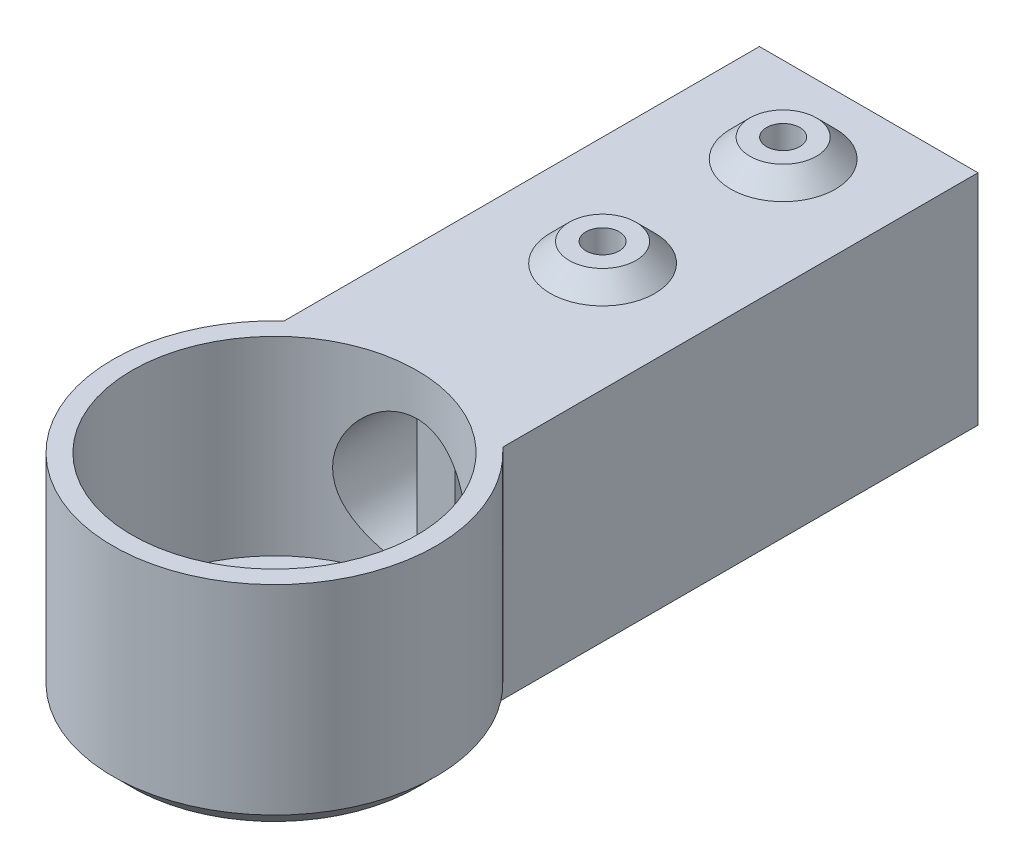
SolidWorks part; units mm, degrees
material "ABS generico"
ref_plane "Piano frontale" through (0, 0, 0) normal (0, 0, 1) x (1, 0, 0)
ref_plane "Piano superiore" through (0, 0, 0) normal (0, 1, 0) x (1, 0, 0)
ref_plane "Piano destro" through (0, 0, 0) normal (1, 0, 0) x (0, 0, -1)
sketch "Schizzo1" plane through (0, 0, 0) normal (0, 0, 1) x (1, 0, 0)
  line L4 (-7.3767, -9.877) -> (-7.3597, -9.8281)
  line L24 (7.9489, 13.813) -> (-15.0511, 13.813)
  line L25 (7.9489, 13.813) -> (7.9489, -9.187)
  line L26 (7.9489, -9.187) -> (-15.0511, -9.187)
  line L27 (-15.0511, 13.813) -> (-15.0511, -9.187)
  dimension "D1" = 23
extrude "Estrusione-Estrusione1" add sketch "Schizzo1" along normal blind 50 contours L24 L27 L26 L25 region at (-3.5511, 2.313, 0)
sketch "Schizzo3" plane through (0, 13.813, 0) normal (0, 1, 0) x (1, 0, 0)
  circle A0 centre (-3.5511, -62.52) radius 17
  dimension "D1" = 34
extrude "Taglio-Estrusione2" cut sketch "Schizzo3" against normal through all
sketch "Schizzo4" plane through (0, 13.813, 0) normal (0, 1, 0) x (1, 0, 0)
  circle A0 centre (-3.5511, -62.52) radius 17
  arc A2 (7.9489, -50) -> (-15.0511, -50) centre (-3.5511, -62.52) ccw construction
  circle A3 centre (-3.5511, -62.52) radius 15 construction
  circle A4 centre (-3.5511, -62.52) radius 15
  dimension "D1" = 34
  dimension "D2" = 30
extrude "Estrusione-Estrusione2" add sketch "Schizzo4" against normal through all contours A4 region at (-20.0702, 13.813, 62.52)
sketch "Schizzo6" plane through (0, -9.187, 0) normal (0, -1, 0) x (1, 0, 0)
  circle A0 centre (-3.5511, 62.52) radius 15
extrude "Estrusione-Estrusione3" add sketch "Schizzo6" against normal blind 2
sketch "Schizzo11" plane through (0, -7.187, 0) normal (0, 1, 0) x (1, 0, 0)
  circle A0 centre (-3.5511, -62.52) radius 15
extrude "Estrusione-Estrusione4" add sketch "Schizzo11" along normal blind 1
chamfer "Smusso2" distance 2 angle 45 1 edges at (-3.5511, -9.187, 79.52)
sketch "Schizzo12" plane through (0, -6.187, 0) normal (0, 1, 0) x (1, 0, 0)
  circle A0 centre (-3.5511, -62.52) radius 2.5
  dimension "D1" = 5
extrude "Taglio-Estrusione6" cut sketch "Schizzo12" against normal through all
sketch "Schizzo13" plane through (0, -6.187, 0) normal (0, 1, 0) x (1, 0, 0)
  circle A0 centre (-3.5511, -62.52) radius 4.75
  circle A1 centre (-3.5511, -62.52) radius 2.5 construction
  dimension "D1" = 9.5
extrude "Taglio-Estrusione7" cut sketch "Schizzo13" against normal blind 2
sketch "Schizzo14" plane through (0, -6.187, 0) normal (0, 1, 0) x (1, 0, 0)
  line L0 (-9.5708, -67.789) -> (2.4686, -57.2509) construction
  line L1 (-9.8081, -55.3716) -> (2.7059, -69.6684) construction
  circle A2 centre (-9.8081, -55.3716) radius 1.5
  circle A3 centre (2.7059, -69.6684) radius 1.5
  circle A7 centre (-9.5708, -67.789) radius 1.5
  circle A8 centre (2.4686, -57.2509) radius 1.5
  circle A9 centre (-3.5511, -62.52) radius 1.1286 construction
  dimension "D3" = 16
  dimension "D5" = 9.5
  dimension "D1" = 3
  dimension "D4" = 8
  dimension "D2" = 19
extrude "Taglio-Estrusione9" cut sketch "Schizzo14" against normal through all contours A2 | A7 | A3 | A8
sketch "Schizzo17" plane through (0, -6.187, 0) normal (0, 1, 0) x (1, 0, 0)
  line L0 (-3.5511, -47.52) -> (-3.5511, -77.52) construction
  line L1 (-18.5511, -62.52) -> (11.4489, -62.52) construction
  line L2 (-5.0347, -69.299) -> (-5.7271, -73.9477)
  line L3 (-2.0674, -69.299) -> (-1.3751, -73.9477)
  line L4 (-3.5511, -77.52) -> (-3.5511, -47.52) construction
  line L5 (-2.0674, -69.299) -> (-5.0347, -69.299) construction
  line L6 (-5.7271, -73.9477) -> (-1.3751, -73.9477) construction
  line L7 (3.228, -64.0036) -> (7.8767, -64.696)
  line L8 (3.228, -61.0363) -> (7.8767, -60.344)
  line L9 (11.4489, -62.52) -> (-18.5511, -62.52) construction
  line L10 (3.228, -61.0363) -> (3.228, -64.0036) construction
  line L11 (7.8767, -64.696) -> (7.8767, -60.344) construction
  line L12 (-10.3301, -64.0036) -> (-10.3301, -61.0363) construction
  line L13 (-10.3301, -61.0363) -> (-14.9788, -60.344)
  line L14 (-10.3301, -64.0036) -> (-14.9788, -64.696)
  line L15 (-14.9788, -60.344) -> (-14.9788, -64.696) construction
  line L16 (-2.0674, -55.741) -> (-1.3751, -51.0922)
  line L17 (-5.0347, -55.741) -> (-5.7271, -51.0922)
  line L18 (-3.5511, -47.52) -> (-3.5511, -77.52) construction
  line L19 (-5.0347, -55.741) -> (-2.0674, -55.741) construction
  line L20 (-1.3751, -51.0922) -> (-5.7271, -51.0922) construction
  circle A0 centre (-3.5511, -62.52) radius 8 construction
  arc A1 (-5.0347, -69.299) -> (-2.0674, -69.299) centre (-3.5511, -69.52) cw
  circle A2 centre (-3.5511, -62.52) radius 9.5 construction
  arc A3 (-1.3751, -73.9477) -> (-5.7271, -73.9477) centre (-3.5511, -74.2718) cw
  circle A4 centre (-3.5511, -62.52) radius 8 construction
  arc A5 (-10.3301, -61.0363) -> (-10.3301, -64.0036) centre (-10.5511, -62.52) cw
  arc A6 (-14.9788, -64.696) -> (-14.9788, -60.344) centre (-15.3029, -62.52) cw
  circle A7 centre (-3.5511, -62.52) radius 15 construction
  circle A8 centre (-3.5511, -62.52) radius 9.5 construction
  arc A9 (3.228, -64.0036) -> (3.228, -61.0363) centre (3.4489, -62.52) cw
  arc A10 (7.8767, -60.344) -> (7.8767, -64.696) centre (8.2008, -62.52) cw
  circle A11 centre (-3.5511, -62.52) radius 8 construction
  circle A12 centre (-3.5511, -62.52) radius 9.5 construction
  arc A13 (-2.0674, -55.741) -> (-5.0347, -55.741) centre (-3.5511, -55.52) cw
  arc A14 (-5.7271, -51.0922) -> (-1.3751, -51.0922) centre (-3.5511, -50.7681) cw
  circle A15 centre (-3.5511, -62.52) radius 8 construction
  circle A16 centre (-3.5511, -62.52) radius 9.5 construction
  point P48 (-3.5511, -62.52)
  dimension "D1" = 4.7
  dimension "D2" = 2.2
  dimension "D3" = 1.5
  dimension "D4" = 7
  dimension "D5" = 4
extrude "Taglio-Estrusione11" cut sketch "Schizzo17" against normal through all
sketch "Schizzo18" plane through (0, 0, 0) normal (0, 0, -1) x (-1, 0, 0)
  line L0 (-7.9489, 2.313) -> (15.0511, 2.313) construction
  line L1 (-7.9489, 13.813) -> (-7.9489, -9.187) construction
  line L2 (15.0511, 13.813) -> (15.0511, -9.187) construction
  line L3 (3.5511, 13.813) -> (3.5511, -9.187) construction
  line L4 (-7.9489, 13.813) -> (15.0511, 13.813) construction
  line L5 (-7.9489, -9.187) -> (15.0511, -9.187) construction
  circle A0 centre (3.5511, 2.313) radius 7.1
  dimension "D1" = 14.2
extrude "Taglio-Estrusione12" cut sketch "Schizzo18" against normal up to next
sketch "Schizzo19" plane through (0, 13.813, 0) normal (0, 1, 0) x (1, 0, 0)
  line L0 (-3.5511, -47.52) -> (-3.5511, -8.3042) construction
  line L2 (-5.5511, -42.52) -> (-1.5511, -42.52)
  line L3 (-5.5511, -42.52) -> (-5.5511, -45.52)
  line L4 (-5.5511, -45.52) -> (-1.5511, -45.52)
  line L5 (-1.5511, -42.52) -> (-1.5511, -45.52)
  circle A0 centre (-3.5511, -62.52) radius 15 construction
  dimension "D1" = 4
  dimension "D2" = 3
  dimension "D3" = 2
  dimension "D4" = 2
extrude "Estrusione-Estrusione5" add sketch "Schizzo19" against normal through all
sketch "Schizzo21" plane through (0, 13.813, 0) normal (0, 1, 0) x (1, 0, 0)
  line L0 (-3.5511, 0) -> (-3.5511, -47.52) construction
  line L1 (7.9489, 0) -> (-15.0511, 0) construction
  circle A0 centre (-3.5511, -62.52) radius 15 construction
  circle A1 centre (-3.5511, -9) radius 5.5
  circle A2 centre (-3.5511, -28) radius 5.5
  point P13 (0, 0)
  dimension "D1" = 11
  dimension "D2" = 19
  dimension "D3" = 9
extrude "Estrusione-Estrusione6" add sketch "Schizzo21" along normal blind 2
sketch "Schizzo20" plane through (0, 15.813, 0) normal (0, 1, 0) x (1, 0, 0)
  line L0 (-3.5511, 0) -> (-3.5511, -47.52) construction
  line L1 (7.9489, 0) -> (-15.0511, 0) construction
  circle A0 centre (-3.5511, -62.52) radius 15 construction
  circle A1 centre (-3.5511, -9) radius 1.75
  circle A2 centre (-3.5511, -28) radius 1.75
  dimension "D1" = 3.5
  dimension "D2" = 9
  dimension "D3" = 19
extrude "Taglio-Estrusione13" cut sketch "Schizzo20" against normal through all
chamfer "Smusso3" distance 2 angle 45 2 edges at (-9.0511, 15.813, 9) (-9.0511, 15.813, 28)
chamfer "Smusso4" distance 1 distance2 3 1 edges at (-10.6511, 2.313, 0) first distance on face at (-10.6511, 2.313, 0)
